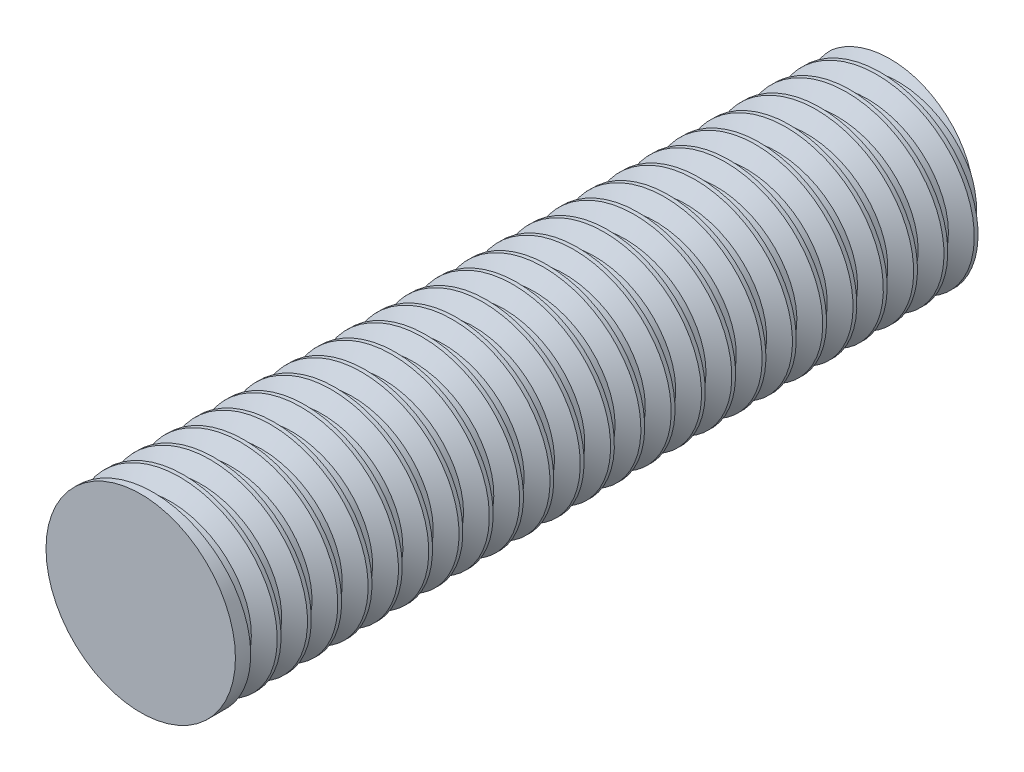
SolidWorks part; units mm, degrees
ref_plane "Plano frontal" through (0, 0, 0) normal (0, 0, 1) x (1, 0, 0)
ref_plane "Plano superior" through (0, 0, 0) normal (0, 1, 0) x (1, 0, 0)
ref_plane "Plano direito" through (0, 0, 0) normal (1, 0, 0) x (0, 0, -1)
sketch "Esboço1" plane through (0, 0, 0) normal (0, 0, 1) x (1, 0, 0)
  circle A0 centre (0, 0) radius 2.5
  dimension "D1" = 5
extrude "Ressalto-extrusão1" add sketch "Esboço1" along normal blind 20
thread "Rosca1" pitch 0.8 method cut profile "Perfil da rosca1" start angle 0, offset 0, length 0, pitch 0.8, diameter 5
ref_plane "Plano1" through (-2.5, 0, 20) normal (0, -1, 0) x (-1, 0, 0)
sketch "Perfil da rosca1" plane through (-2.5, 0, 20) normal (0, -1, 0) x (-1, 0, 0)
  line L0 (0, 0) -> (0, 0.8) construction
  line L11 (0, 0) -> (0, 0.7)
  line L12 (0, 0.7) -> (-0.433, 0.45)
  line L13 (-0.433, 0.45) -> (-0.433, 0.25)
  line L15 (-0.433, 0.25) -> (0, 0)
  line L17 (-0.433, 0.35) -> (0, 0.35) construction
  point P2 (0, 0)
  dimension "Pitch" = 0.8
  dimension "Profile_Angle" = 60
  dimension "Profile_Land" = 0.2
  dimension "Profile_Height" = 0.433
